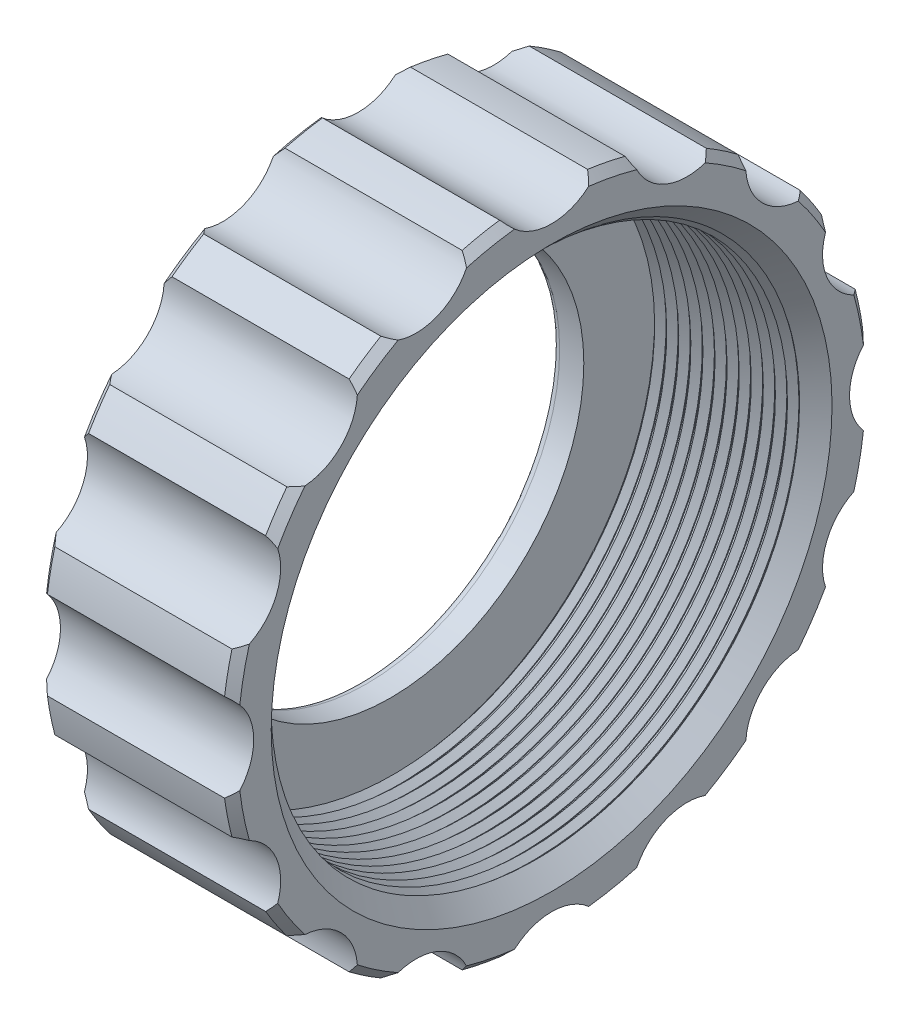
SolidWorks part; units mm, degrees
ref_plane "Front Plane" through (0, 0, 0) normal (0, 0, 1) x (1, 0, 0)
ref_plane "Top Plane" through (0, 0, 0) normal (0, 1, 0) x (1, 0, 0)
ref_plane "Right Plane" through (0, 0, 0) normal (1, 0, 0) x (0, 0, -1)
sketch "Sketch1" plane through (0, 0, 0) normal (0, 0, 1) x (1, 0, 0)
  line L0 (0, 0) -> (33.0241, 0) construction
  line L1 (0, 24) -> (0, 40)
  line L2 (0, 40) -> (24, 40)
  line L3 (24, 40) -> (24, 33)
  line L4 (24, 33) -> (4, 33)
  line L5 (4, 33) -> (4, 24)
  line L6 (4, 24) -> (0, 24)
  dimension "D1" = 40
  dimension "D2" = 33
  dimension "D3" = 24
  dimension "D4" = 4
  dimension "D5" = 20
revolve "Revolve1" add sketch "Sketch1" angle 360 about L0
chamfer "Chamfer1" distance 1 angle 45 2 edges at (24, 0, 40) (0, 0, 40)
sketch "Sketch2" plane through (0, 0, 0) normal (-1, 0, 0) x (0, 0, 1)
  line L0 (0, 44) -> (0, 0) construction
  circle A1 centre (0, 44) radius 7
  point P0 (0, 43.5716)
  dimension "D1" = 14
  dimension "D2" = 44
extrude "Cut-Extrude1" cut sketch "Sketch2" against normal through all
pattern_circular "CirPattern1" count 16 over 360 about axis through (0, 0, 0) along (-1, 0, 0) of "Cut-Extrude1" reverse direction yes
sketch "Sketch3" plane through (24, 0, 0) normal (1, 0, 0) x (0, 0, -1)
  circle A0 centre (0, 0) radius 33 construction
  circle A1 centre (0, 0) radius 33
curve "Helix/Spiral1" pitch 1.5 height 20 radius 33 centre (24, 0, 0) axis (-1, 0, 0) start towards (0, 0, -1)
sketch "Sketch4" plane through (0, 0, 0) normal (0, 1, 0) x (1, 0, 0)
  line L0 (24, 32.2929) -> (24.7071, 33)
  line L1 (24, 32.2929) -> (23.2929, 33)
  line L2 (24.7071, 33) -> (24, 33.7071)
  line L3 (23.2929, 33) -> (24, 33.7071)
  line L4 (24, 32.2929) -> (24, 33.7071) construction
  line L5 (24.7071, 33) -> (23.2929, 33) construction
  line L6 (24, -33) -> (24, 33) construction
  spline S0 degree 3 poles (19.9268, -1966.8583) (25.5026, -408.9549) (24.6838, 69.8235) (23.882, 29.3479) (23.823, 24.5878) (23.764, 18.3337) (23.705, 10.9656) (23.646, 2.9312) (23.587, -5.2813) (23.528, -13.1728) (23.469, -20.264) (23.41, -26.1239) (23.351, -30.3965) (23.292, -32.8222) (23.233, -33.2535) (23.174, -31.6643) (23.115, -28.1512) (23.056, -22.9275) (22.9971, -16.3108) (22.9381, -8.703) (22.8791, -0.5664) (22.8201, 7.6047) (22.7611, 15.3136) (22.7021, 22.0921) (22.6431, 27.5282) (22.5841, 31.2917) (22.5251, 33.1539) (22.4661, 33.0016) (22.4071, 30.8441) (22.3481, 26.8124) (22.2891, 21.1516) (22.2301, 14.2056) (22.1711, 6.3965) (22.1121, -1.8013) (22.0531, -9.8897) (21.9941, -17.3771) (21.9351, -23.8087) (21.8761, -28.7937) (21.8171, -32.0291) (21.7581, -33.3184) (21.6991, -32.5832) (21.6401, -29.8682) (21.5811, -25.3384) (21.5221, -19.269) (21.4631, -12.0288) (21.4041, -4.0577) (21.3451, 4.1599) (21.2861, 12.1248) (21.2271, 19.353) (21.1681, 25.4052) (21.1091, 29.9138) (21.0501, 32.6048) (20.9912, 33.3147) (20.9322, 32.0004) (20.8732, 28.7416) (20.8142, 23.7365) (20.7552, 17.2892) (20.6962, 9.7913) (20.6372, 1.6985) (20.5782, -6.4975) (20.5192, -14.2987) (20.4602, -21.2311) (20.4012, -26.8735) (20.3422, -30.883) (20.2832, -33.016) (20.2242, -33.1429) (20.1652, -31.2561) (20.1062, -27.47) (20.0472, -22.0149) (19.9882, -15.2221) (19.9292, -7.5043) (19.8702, 0.6693) (19.8112, 8.8024) (19.7522, 16.4005) (19.6932, 23.0022) (19.6342, 28.2062) (19.5752, 31.6964) (19.5162, 33.2606) (19.4572, 32.804) (19.3982, 30.3541) (19.3392, 26.0598) (19.2802, 20.1821) (19.2212, 13.0782) (19.1622, 5.1795) (19.1032, -3.0338) (19.0442, -11.0628) (18.9853, -18.4196) (18.9263, -24.6572) (18.8673, -29.3966) (18.8083, -32.3498) (18.7493, -33.3374) (18.6903, -32.2994) (18.6313, -29.2989) (18.5723, -24.5181) (18.5133, -18.2476) (18.4543, -10.8683) (18.3953, -2.8286) (18.3363, 5.3829) (18.2773, 13.2674) (18.2183, 20.3457) (18.1593, 26.1878) (18.1003, 30.4386) (18.0413, 32.84) (17.9823, 33.246) (17.9233, 31.632) (17.8643, 28.0959) (17.8053, 22.8527) (17.7463, 16.2209) (17.6873, 8.6035) (17.6283, 0.4634) (17.5693, -7.7049) (17.5103, -15.405) (17.4513, -22.1691) (17.3923, -27.5862) (17.3333, -31.3271) (17.2743, -33.1645) (17.2153, -32.9869) (17.1563, -30.8049) (17.0973, -26.7511) (17.0383, -21.0719) (16.9794, -14.1124) (16.9204, -6.2954) (16.8614, 1.9041) (16.8024, 9.988) (16.7434, 17.4649) (16.6844, 23.8807) (16.6254, 28.8454) (16.5664, 32.0575) (16.5074, 33.3217) (16.4484, 32.5612) (16.3894, 29.8223) (16.3304, 25.2714) (16.2714, 19.1849) (16.2124, 11.9327) (16.1534, 3.9555) (16.0944, -4.2621) (16.0354, -12.2207) (15.9764, -19.4367) (15.9174, -25.4718) (15.8584, -29.9591) (15.7994, -32.6261) (15.7404, -33.3107) (15.6814, -31.9713) (15.6224, -28.6893) (15.5634, -23.6641) (15.5044, -17.201) (15.4454, -9.6928) (15.3864, -1.5956) (15.3274, 6.5985) (15.2684, 14.3917) (15.2094, 21.3104) (15.1504, 26.9343) (15.0914, 30.9216) (15.0324, 33.0301) (14.9735, 33.1317) (14.9145, 31.2201) (14.8555, 27.4115) (14.7965, 21.9374) (14.7375, 15.1304) (14.6785, 7.404) (14.6195, -0.7723) (14.5605, -8.9016) (14.5015, -16.4901) (14.4425, -23.0766) (14.3835, -28.261) (14.3245, -31.7281) (14.2655, -33.2675) (14.2065, -32.7854) (14.1475, -30.3113) (14.0885, -25.9955) (14.0295, -20.1001) (13.9705, -12.9834) (13.9115, -5.0778) (13.8525, 3.1363) (13.7935, 11.1599) (13.7345, 18.5053) (13.6755, 24.7264) (13.6165, 29.445) (13.5575, 32.3746) (13.4985, 33.337) (13.4395, 32.2738) (13.3805, 29.2496) (13.3215, 24.4482) (13.2625, 18.1613) (13.2035, 10.7709) (13.1445, 2.726) (13.0855, -5.4845) (13.0265, -13.3618) (12.9676, -20.4272) (12.9086, -26.2514) (12.8496, -30.4805) (12.7906, -32.8576) (12.7316, -33.2382) (12.6726, -31.5993) (12.6136, -28.0403) (12.5546, -22.7776) (12.4956, -16.1309) (12.4366, -8.504) (12.3776, -0.3604) (12.3186, 7.805) (12.2596, 15.4963) (12.2006, 22.2459) (12.1416, 27.6439) (12.0826, 31.3622) (12.0236, 33.1749) (11.9646, 32.9718) (11.9056, 30.7653) (11.8466, 26.6895) (11.7876, 20.992) (11.7286, 14.019) (11.6696, 6.1942) (11.6106, -2.0069) (11.5516, -10.0862) (11.4926, -17.5526) (11.4336, -23.9524) (11.3746, -28.8969) (11.3156, -32.0856) (11.2566, -33.3247) (11.1976, -32.539) (11.1386, -29.7762) (11.0796, -25.2041) (11.0206, -19.1006) (10.9617, -11.8365) (10.9027, -3.8532) (10.8437, 4.3642) (10.7847, 12.3164) (10.7257, 19.5203) (10.6667, 25.5381) (10.6077, 30.0042) (10.5487, 32.6471) (10.4897, 33.3064) (10.4307, 31.942) (10.3717, 28.6367) (10.3127, 23.5914) (10.2537, 17.1127) (10.1947, 9.5942) (10.1357, 1.4927) (10.0767, -6.6994) (10.0177, -14.4845) (9.9587, -21.3895) (9.8997, -26.9949) (9.8407, -30.96) (9.7817, -33.0439) (9.7227, -33.1201) (9.6637, -31.1838) (9.6047, -27.3528) (9.5457, -21.8598) (9.4867, -15.0385) (9.4277, -7.3035) (9.3687, 0.8753) (9.3097, 9.0008) (9.2507, 16.5795) (9.1917, 23.1508) (9.1327, 28.3155) (9.0737, 31.7596) (9.0147, 33.274) (8.9558, 32.7666) (8.8968, 30.2683) (8.8378, 25.9309) (8.7788, 20.0178) (8.7198, 12.8885) (8.6608, 4.976) (8.6018, -3.2388) (8.5428, -11.2569) (8.4838, -18.5909) (8.4248, -24.7953) (8.3658, -29.4932) (8.3068, -32.399) (8.2478, -33.3362) (8.1888, -32.2478) (8.1298, -29.2001) (8.0708, -24.3781) (8.0118, -18.0748) (7.9528, -10.6733) (7.8938, -2.6233) (7.8348, 5.5861) (7.7758, 13.4561) (7.7168, 20.5084) (7.6578, 26.3147) (7.5988, 30.5221) (7.5398, 32.8749) (7.4808, 33.2301) (7.4218, 31.5663) (7.3628, 27.9845) (7.3038, 22.7023) (7.2448, 16.0407) (7.1858, 8.4044) (7.1268, 0.2575) (7.0678, -7.9051) (7.0088, -15.5874) (6.9499, -22.3225) (6.8909, -27.7013) (6.8319, -31.3969) (6.7729, -33.1849) (6.7139, -32.9564) (6.6549, -30.7255) (6.5959, -26.6277) (6.5369, -20.9119) (6.4779, -13.9255) (6.4189, -6.093) (6.3599, 2.1097) (6.3009, 10.1843) (6.2419, 17.64) (6.1829, 24.0239) (6.1239, 28.9481) (6.0649, 32.1134) (6.0059, 33.3274) (5.9469, 32.5164) (5.8879, 29.7297) (5.8289, 25.1365) (5.7699, 19.0161) (5.7109, 11.7402) (5.6519, 3.7509) (5.5929, -4.4663) (5.5339, -12.4121) (5.4749, -19.6037) (5.4159, -25.6042) (5.3569, -30.0489) (5.2979, -32.6678) (5.2389, -33.3018) (5.1799, -31.9124) (5.1209, -28.5839) (5.0619, -23.5186) (5.0029, -17.0243) (4.944, -9.4955) (4.885, -1.3899) (4.826, 6.8003) (4.767, 14.5772) (4.708, 21.4684) (4.649, 27.0552) (4.59, 30.998) (4.531, 33.0574) (4.472, 33.1082) (4.413, 31.1473) (4.354, 27.2938) (4.295, 21.7819) (4.236, 14.9465) (4.177, 7.2032) (4.118, -0.9789) (3.5254, -82.5669) (2.9327, -85.4858) (4.7914, 1983.0838) knots -0.111474 -0.111474 -0.111474 -0.111474 0.00295 0.0059 0.00885 0.011799 0.014749 0.017699 0.020649 0.023599 0.026549 0.029499 0.032448 0.035398 0.038348 0.041298 0.044248 0.047198 0.050147 0.053097 0.056047 0.058997 0.061947 0.064897 0.067847 0.070796 0.073746 0.076696 0.079646 0.082596 0.085546 0.088496 0.091445 0.094395 0.097345 0.100295 0.103245 0.106195 0.109145 0.112094 0.115044 0.117994 0.120944 0.123894 0.126844 0.129794 0.132743 0.135693 0.138643 0.141593 0.144543 0.147493 0.150442 0.153392 0.156342 0.159292 0.162242 0.165192 0.168142 0.171091 0.174041 0.176991 0.179941 0.182891 0.185841 0.188791 0.19174 0.19469 0.19764 0.20059 0.20354 0.20649 0.20944 0.212389 0.215339 0.218289 0.221239 0.224189 0.227139 0.230088 0.233038 0.235988 0.238938 0.241888 0.244838 0.247788 0.250737 0.253687 0.256637 0.259587 0.262537 0.265487 0.268437 0.271386 0.274336 0.277286 0.280236 0.283186 0.286136 0.289086 0.292035 0.294985 0.297935 0.300885 0.303835 0.306785 0.309735 0.312684 0.315634 0.318584 0.321534 0.324484 0.327434 0.330383 0.333333 0.336283 0.339233 0.342183 0.345133 0.348083 0.351032 0.353982 0.356932 0.359882 0.362832 0.365782 0.368732 0.371681 0.374631 0.377581 0.380531 0.383481 0.386431 0.389381 0.39233 0.39528 0.39823 0.40118 0.40413 0.40708 0.410029 0.412979 0.415929 0.418879 0.421829 0.424779 0.427729 0.430678 0.433628 0.436578 0.439528 0.442478 0.445428 0.448378 0.451327 0.454277 0.457227 0.460177 0.463127 0.466077 0.469027 0.471976 0.474926 0.477876 0.480826 0.483776 0.486726 0.489676 0.492625 0.495575 0.498525 0.501475 0.504425 0.507375 0.510324 0.513274 0.516224 0.519174 0.522124 0.525074 0.528024 0.530973 0.533923 0.536873 0.539823 0.542773 0.545723 0.548673 0.551622 0.554572 0.557522 0.560472 0.563422 0.566372 0.569322 0.572271 0.575221 0.578171 0.581121 0.584071 0.587021 0.589971 0.59292 0.59587 0.59882 0.60177 0.60472 0.60767 0.610619 0.613569 0.616519 0.619469 0.622419 0.625369 0.628319 0.631268 0.634218 0.637168 0.640118 0.643068 0.646018 0.648968 0.651917 0.654867 0.657817 0.660767 0.663717 0.666667 0.669617 0.672566 0.675516 0.678466 0.681416 0.684366 0.687316 0.690265 0.693215 0.696165 0.699115 0.702065 0.705015 0.707965 0.710914 0.713864 0.716814 0.719764 0.722714 0.725664 0.728614 0.731563 0.734513 0.737463 0.740413 0.743363 0.746313 0.749263 0.752212 0.755162 0.758112 0.761062 0.764012 0.766962 0.769912 0.772861 0.775811 0.778761 0.781711 0.784661 0.787611 0.79056 0.79351 0.79646 0.79941 0.80236 0.80531 0.80826 0.811209 0.814159 0.817109 0.820059 0.823009 0.825959 0.828909 0.831858 0.834808 0.837758 0.840708 0.843658 0.846608 0.849558 0.852507 0.855457 0.858407 0.861357 0.864307 0.867257 0.870206 0.873156 0.876106 0.879056 0.882006 0.884956 0.887906 0.890855 0.893805 0.896755 0.899705 0.902655 0.905605 0.908555 0.911504 0.914454 0.917404 0.920354 0.923304 0.926254 0.929204 0.932153 0.935103 0.938053 0.941003 0.943953 0.946903 0.949853 0.952802 0.955752 0.958702 0.961652 0.964602 0.967552 0.970501 0.973451 0.976401 0.979351 0.982301 0.985251 0.988201 0.99115 0.9941 0.99705 1.080088 1.080088 1.080088 1.080088 only from (24, 33) to (4, -16.5) construction
  spline S1 degree 3 poles (24, 33) (23.9804, 33) (23.941, 32.3248) (23.882, 29.3479) (23.823, 24.5878) (23.764, 18.3337) (23.705, 10.9656) (23.646, 2.9312) (23.587, -5.2813) (23.528, -13.1728) (23.469, -20.264) (23.41, -26.1239) (23.351, -30.3965) (23.292, -32.8222) (23.233, -33.2535) (23.174, -31.6643) (23.115, -28.1512) (23.056, -22.9275) (22.9971, -16.3108) (22.9381, -8.703) (22.8791, -0.5664) (22.8201, 7.6047) (22.7611, 15.3136) (22.7021, 22.0921) (22.6431, 27.5282) (22.5841, 31.2917) (22.5251, 33.1539) (22.4661, 33.0016) (22.4071, 30.8441) (22.3481, 26.8124) (22.2891, 21.1516) (22.2301, 14.2056) (22.1711, 6.3965) (22.1121, -1.8013) (22.0531, -9.8897) (21.9941, -17.3771) (21.9351, -23.8087) (21.8761, -28.7937) (21.8171, -32.0291) (21.7581, -33.3184) (21.6991, -32.5832) (21.6401, -29.8682) (21.5811, -25.3384) (21.5221, -19.269) (21.4631, -12.0288) (21.4041, -4.0577) (21.3451, 4.1599) (21.2861, 12.1248) (21.2271, 19.353) (21.1681, 25.4052) (21.1091, 29.9138) (21.0501, 32.6048) (20.9912, 33.3147) (20.9322, 32.0004) (20.8732, 28.7416) (20.8142, 23.7365) (20.7552, 17.2892) (20.6962, 9.7913) (20.6372, 1.6985) (20.5782, -6.4975) (20.5192, -14.2987) (20.4602, -21.2311) (20.4012, -26.8735) (20.3422, -30.883) (20.2832, -33.016) (20.2242, -33.1429) (20.1652, -31.2561) (20.1062, -27.47) (20.0472, -22.0149) (19.9882, -15.2221) (19.9292, -7.5043) (19.8702, 0.6693) (19.8112, 8.8024) (19.7522, 16.4005) (19.6932, 23.0022) (19.6342, 28.2062) (19.5752, 31.6964) (19.5162, 33.2606) (19.4572, 32.804) (19.3982, 30.3541) (19.3392, 26.0598) (19.2802, 20.1821) (19.2212, 13.0782) (19.1622, 5.1795) (19.1032, -3.0338) (19.0442, -11.0628) (18.9853, -18.4196) (18.9263, -24.6572) (18.8673, -29.3966) (18.8083, -32.3498) (18.7493, -33.3374) (18.6903, -32.2994) (18.6313, -29.2989) (18.5723, -24.5181) (18.5133, -18.2476) (18.4543, -10.8683) (18.3953, -2.8286) (18.3363, 5.3829) (18.2773, 13.2674) (18.2183, 20.3457) (18.1593, 26.1878) (18.1003, 30.4386) (18.0413, 32.84) (17.9823, 33.246) (17.9233, 31.632) (17.8643, 28.0959) (17.8053, 22.8527) (17.7463, 16.2209) (17.6873, 8.6035) (17.6283, 0.4634) (17.5693, -7.7049) (17.5103, -15.405) (17.4513, -22.1691) (17.3923, -27.5862) (17.3333, -31.3271) (17.2743, -33.1645) (17.2153, -32.9869) (17.1563, -30.8049) (17.0973, -26.7511) (17.0383, -21.0719) (16.9794, -14.1124) (16.9204, -6.2954) (16.8614, 1.9041) (16.8024, 9.988) (16.7434, 17.4649) (16.6844, 23.8807) (16.6254, 28.8454) (16.5664, 32.0575) (16.5074, 33.3217) (16.4484, 32.5612) (16.3894, 29.8223) (16.3304, 25.2714) (16.2714, 19.1849) (16.2124, 11.9327) (16.1534, 3.9555) (16.0944, -4.2621) (16.0354, -12.2207) (15.9764, -19.4367) (15.9174, -25.4718) (15.8584, -29.9591) (15.7994, -32.6261) (15.7404, -33.3107) (15.6814, -31.9713) (15.6224, -28.6893) (15.5634, -23.6641) (15.5044, -17.201) (15.4454, -9.6928) (15.3864, -1.5956) (15.3274, 6.5985) (15.2684, 14.3917) (15.2094, 21.3104) (15.1504, 26.9343) (15.0914, 30.9216) (15.0324, 33.0301) (14.9735, 33.1317) (14.9145, 31.2201) (14.8555, 27.4115) (14.7965, 21.9374) (14.7375, 15.1304) (14.6785, 7.404) (14.6195, -0.7723) (14.5605, -8.9016) (14.5015, -16.4901) (14.4425, -23.0766) (14.3835, -28.261) (14.3245, -31.7281) (14.2655, -33.2675) (14.2065, -32.7854) (14.1475, -30.3113) (14.0885, -25.9955) (14.0295, -20.1001) (13.9705, -12.9834) (13.9115, -5.0778) (13.8525, 3.1363) (13.7935, 11.1599) (13.7345, 18.5053) (13.6755, 24.7264) (13.6165, 29.445) (13.5575, 32.3746) (13.4985, 33.337) (13.4395, 32.2738) (13.3805, 29.2496) (13.3215, 24.4482) (13.2625, 18.1613) (13.2035, 10.7709) (13.1445, 2.726) (13.0855, -5.4845) (13.0265, -13.3618) (12.9676, -20.4272) (12.9086, -26.2514) (12.8496, -30.4805) (12.7906, -32.8576) (12.7316, -33.2382) (12.6726, -31.5993) (12.6136, -28.0403) (12.5546, -22.7776) (12.4956, -16.1309) (12.4366, -8.504) (12.3776, -0.3604) (12.3186, 7.805) (12.2596, 15.4963) (12.2006, 22.2459) (12.1416, 27.6439) (12.0826, 31.3622) (12.0236, 33.1749) (11.9646, 32.9718) (11.9056, 30.7653) (11.8466, 26.6895) (11.7876, 20.992) (11.7286, 14.019) (11.6696, 6.1942) (11.6106, -2.0069) (11.5516, -10.0862) (11.4926, -17.5526) (11.4336, -23.9524) (11.3746, -28.8969) (11.3156, -32.0856) (11.2566, -33.3247) (11.1976, -32.539) (11.1386, -29.7762) (11.0796, -25.2041) (11.0206, -19.1006) (10.9617, -11.8365) (10.9027, -3.8532) (10.8437, 4.3642) (10.7847, 12.3164) (10.7257, 19.5203) (10.6667, 25.5381) (10.6077, 30.0042) (10.5487, 32.6471) (10.4897, 33.3064) (10.4307, 31.942) (10.3717, 28.6367) (10.3127, 23.5914) (10.2537, 17.1127) (10.1947, 9.5942) (10.1357, 1.4927) (10.0767, -6.6994) (10.0177, -14.4845) (9.9587, -21.3895) (9.8997, -26.9949) (9.8407, -30.96) (9.7817, -33.0439) (9.7227, -33.1201) (9.6637, -31.1838) (9.6047, -27.3528) (9.5457, -21.8598) (9.4867, -15.0385) (9.4277, -7.3035) (9.3687, 0.8753) (9.3097, 9.0008) (9.2507, 16.5795) (9.1917, 23.1508) (9.1327, 28.3155) (9.0737, 31.7596) (9.0147, 33.274) (8.9558, 32.7666) (8.8968, 30.2683) (8.8378, 25.9309) (8.7788, 20.0178) (8.7198, 12.8885) (8.6608, 4.976) (8.6018, -3.2388) (8.5428, -11.2569) (8.4838, -18.5909) (8.4248, -24.7953) (8.3658, -29.4932) (8.3068, -32.399) (8.2478, -33.3362) (8.1888, -32.2478) (8.1298, -29.2001) (8.0708, -24.3781) (8.0118, -18.0748) (7.9528, -10.6733) (7.8938, -2.6233) (7.8348, 5.5861) (7.7758, 13.4561) (7.7168, 20.5084) (7.6578, 26.3147) (7.5988, 30.5221) (7.5398, 32.8749) (7.4808, 33.2301) (7.4218, 31.5663) (7.3628, 27.9845) (7.3038, 22.7023) (7.2448, 16.0407) (7.1858, 8.4044) (7.1268, 0.2575) (7.0678, -7.9051) (7.0088, -15.5874) (6.9499, -22.3225) (6.8909, -27.7013) (6.8319, -31.3969) (6.7729, -33.1849) (6.7139, -32.9564) (6.6549, -30.7255) (6.5959, -26.6277) (6.5369, -20.9119) (6.4779, -13.9255) (6.4189, -6.093) (6.3599, 2.1097) (6.3009, 10.1843) (6.2419, 17.64) (6.1829, 24.0239) (6.1239, 28.9481) (6.0649, 32.1134) (6.0059, 33.3274) (5.9469, 32.5164) (5.8879, 29.7297) (5.8289, 25.1365) (5.7699, 19.0161) (5.7109, 11.7402) (5.6519, 3.7509) (5.5929, -4.4663) (5.5339, -12.4121) (5.4749, -19.6037) (5.4159, -25.6042) (5.3569, -30.0489) (5.2979, -32.6678) (5.2389, -33.3018) (5.1799, -31.9124) (5.1209, -28.5839) (5.0619, -23.5186) (5.0029, -17.0243) (4.944, -9.4955) (4.885, -1.3899) (4.826, 6.8003) (4.767, 14.5772) (4.708, 21.4684) (4.649, 27.0552) (4.59, 30.998) (4.531, 33.0574) (4.472, 33.1082) (4.413, 31.1473) (4.354, 27.2938) (4.295, 21.7819) (4.236, 14.9465) (4.177, 7.2032) (4.118, -0.9789) (4.059, -9.0972) (4.0196, -14.1518) (4, -16.5) knots 0 0 0 0 0.00295 0.0059 0.00885 0.011799 0.014749 0.017699 0.020649 0.023599 0.026549 0.029499 0.032448 0.035398 0.038348 0.041298 0.044248 0.047198 0.050147 0.053097 0.056047 0.058997 0.061947 0.064897 0.067847 0.070796 0.073746 0.076696 0.079646 0.082596 0.085546 0.088496 0.091445 0.094395 0.097345 0.100295 0.103245 0.106195 0.109145 0.112094 0.115044 0.117994 0.120944 0.123894 0.126844 0.129794 0.132743 0.135693 0.138643 0.141593 0.144543 0.147493 0.150442 0.153392 0.156342 0.159292 0.162242 0.165192 0.168142 0.171091 0.174041 0.176991 0.179941 0.182891 0.185841 0.188791 0.19174 0.19469 0.19764 0.20059 0.20354 0.20649 0.20944 0.212389 0.215339 0.218289 0.221239 0.224189 0.227139 0.230088 0.233038 0.235988 0.238938 0.241888 0.244838 0.247788 0.250737 0.253687 0.256637 0.259587 0.262537 0.265487 0.268437 0.271386 0.274336 0.277286 0.280236 0.283186 0.286136 0.289086 0.292035 0.294985 0.297935 0.300885 0.303835 0.306785 0.309735 0.312684 0.315634 0.318584 0.321534 0.324484 0.327434 0.330383 0.333333 0.336283 0.339233 0.342183 0.345133 0.348083 0.351032 0.353982 0.356932 0.359882 0.362832 0.365782 0.368732 0.371681 0.374631 0.377581 0.380531 0.383481 0.386431 0.389381 0.39233 0.39528 0.39823 0.40118 0.40413 0.40708 0.410029 0.412979 0.415929 0.418879 0.421829 0.424779 0.427729 0.430678 0.433628 0.436578 0.439528 0.442478 0.445428 0.448378 0.451327 0.454277 0.457227 0.460177 0.463127 0.466077 0.469027 0.471976 0.474926 0.477876 0.480826 0.483776 0.486726 0.489676 0.492625 0.495575 0.498525 0.501475 0.504425 0.507375 0.510324 0.513274 0.516224 0.519174 0.522124 0.525074 0.528024 0.530973 0.533923 0.536873 0.539823 0.542773 0.545723 0.548673 0.551622 0.554572 0.557522 0.560472 0.563422 0.566372 0.569322 0.572271 0.575221 0.578171 0.581121 0.584071 0.587021 0.589971 0.59292 0.59587 0.59882 0.60177 0.60472 0.60767 0.610619 0.613569 0.616519 0.619469 0.622419 0.625369 0.628319 0.631268 0.634218 0.637168 0.640118 0.643068 0.646018 0.648968 0.651917 0.654867 0.657817 0.660767 0.663717 0.666667 0.669617 0.672566 0.675516 0.678466 0.681416 0.684366 0.687316 0.690265 0.693215 0.696165 0.699115 0.702065 0.705015 0.707965 0.710914 0.713864 0.716814 0.719764 0.722714 0.725664 0.728614 0.731563 0.734513 0.737463 0.740413 0.743363 0.746313 0.749263 0.752212 0.755162 0.758112 0.761062 0.764012 0.766962 0.769912 0.772861 0.775811 0.778761 0.781711 0.784661 0.787611 0.79056 0.79351 0.79646 0.79941 0.80236 0.80531 0.80826 0.811209 0.814159 0.817109 0.820059 0.823009 0.825959 0.828909 0.831858 0.834808 0.837758 0.840708 0.843658 0.846608 0.849558 0.852507 0.855457 0.858407 0.861357 0.864307 0.867257 0.870206 0.873156 0.876106 0.879056 0.882006 0.884956 0.887906 0.890855 0.893805 0.896755 0.899705 0.902655 0.905605 0.908555 0.911504 0.914454 0.917404 0.920354 0.923304 0.926254 0.929204 0.932153 0.935103 0.938053 0.941003 0.943953 0.946903 0.949853 0.952802 0.955752 0.958702 0.961652 0.964602 0.967552 0.970501 0.973451 0.976401 0.979351 0.982301 0.985251 0.988201 0.99115 0.9941 0.99705 1 1 1 1 construction
  point P2 (24, 33.7071)
  point P3 (23.2929, 33)
  point P4 (24.0047, 32.9937)
  point P10 (0, 0)
  point P11 (24.0239, 33.5388)
  point P12 (24.0604, 31.9069)
  dimension "D1" = 1
sweep "Sweep1" add profiles "Sketch4" path "Helix/Spiral1"
sketch "Sketch5" plane through (0, 0, 0) normal (0, 0, 1) x (1, 0, 0)
  line L0 (21.1716, -32) -> (24, -34.8284)
  line L1 (21.1716, -32) -> (24, -29.1716)
  line L2 (24, -34.8284) -> (26.8284, -32)
  line L3 (24, -29.1716) -> (26.8284, -32)
  line L4 (21.1716, -32) -> (26.8284, -32) construction
  line L5 (24, -34.8284) -> (24, -29.1716) construction
  line L6 (24, 30.64) -> (24, 34.0174) construction
  line L7 (0, 0) -> (75.4988, 0) construction
  point P1 (24, -32)
  dimension "D1" = 4
  dimension "D2" = 32
revolve "Cut-Revolve1" cut sketch "Sketch5" angle 360 about L7
fillet "Fillet1" radius 1 1 edges at (0, 0, 24)
